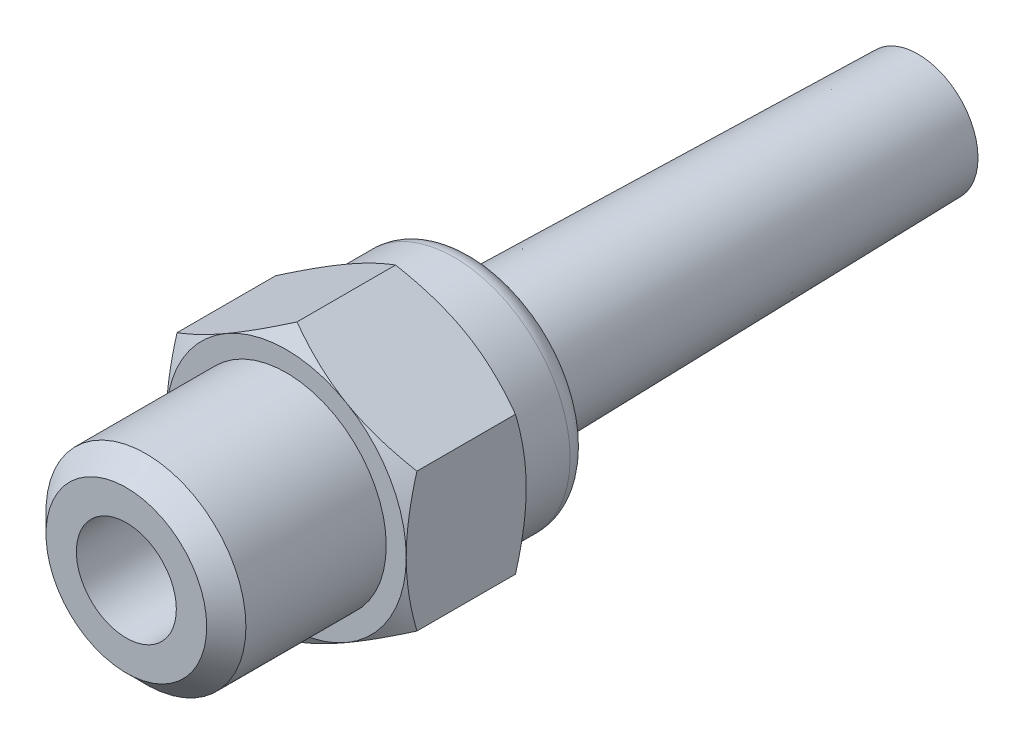
SolidWorks part; units mm, degrees
ref_plane "Front Plane" through (0, 0, 0) normal (0, 0, 1) x (1, 0, 0)
ref_plane "Top Plane" through (0, 0, 0) normal (0, 1, 0) x (1, 0, 0)
ref_plane "Right Plane" through (0, 0, 0) normal (1, 0, 0) x (0, 0, -1)
ref_plane "Plane1" through (0, 0, 0) normal (1, 0, 0) x (0, 0, -1)
sketch "Sketch1" plane through (0, 0, 0) normal (1, 0, 0) x (0, 0, -1)
  line L0 (4, 0) -> (4, 1.25)
  line L1 (4, 1.25) -> (0, 1.25)
  line L2 (0, 1.25) -> (0, 2.0095)
  line L3 (0, 2.0095) -> (0.4905, 2.5)
  line L4 (0.4905, 2.5) -> (4, 2.5)
  line L5 (4, 2.5) -> (4, 3)
  line L6 (4, 3) -> (4.3464, 3.6)
  line L7 (4.3464, 3.6) -> (6.6536, 3.6)
  line L8 (6.6536, 3.6) -> (7, 3)
  line L9 (7, 3) -> (7, 2.9)
  line L10 (7, 2.9) -> (8.2, 2.9)
  line L11 (8.7, 2.4) -> (8.7, 1.7415)
  line L12 (8.7, 1.7415) -> (19.8, 1.5)
  line L13 (19.8, 1.5) -> (19.8, 0)
  line L14 (19.8, 0) -> (4, 0)
  line L15 (19.8, 0) -> (0, 0) construction
  arc A0 (8.2, 2.9) -> (8.7, 2.4) centre (8.2, 2.4) cw
revolve "Revolve1" add sketch "Sketch1" angle 360 about L15 reverse direction yes
cosmetic thread "Cosmetic Thread1" parameters "D1"=4, "D2"=4.019
ref_plane "Plane2" through (0, 0, -4) normal (0, 0, 1) x (1, 0, 0)
sketch "Sketch2" plane through (0, 0, -4) normal (0, 0, 1) x (1, 0, 0)
  line L0 (-6, 6) -> (-6, -6)
  line L1 (-6, -6) -> (6, -6)
  line L2 (6, -6) -> (6, 6)
  line L3 (6, 6) -> (-6, 6)
  line L4 (-3, -1.7321) -> (0, -3.4641)
  line L5 (0, -3.4641) -> (3, -1.7321)
  line L6 (3, -1.7321) -> (3, 1.7321)
  line L7 (3, 1.7321) -> (0, 3.4641)
  line L8 (0, 3.4641) -> (-3, 1.7321)
  line L9 (-3, 1.7321) -> (-3, -1.7321)
extrude "Cut-Extrude1" cut sketch "Sketch2" against normal blind 3
